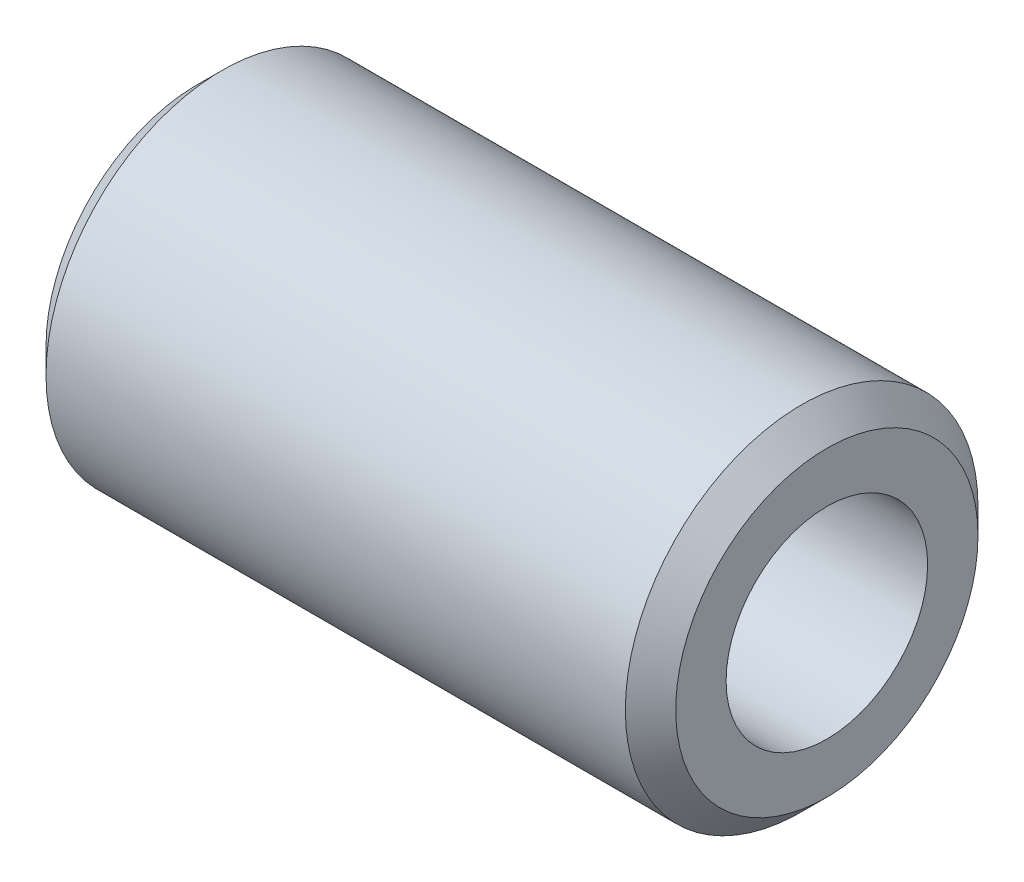
SolidWorks part; units mm, degrees
material "Nylon 101"
ref_plane "Спереди" through (0, 0, 0) normal (0, 0, 1) x (1, 0, 0)
ref_plane "Сверху" through (0, 0, 0) normal (0, 1, 0) x (1, 0, 0)
ref_plane "Справа" through (0, 0, 0) normal (1, 0, 0) x (0, 0, -1)
sketch "Эскиз1" plane through (0, 0, 0) normal (0, 0, 1) x (1, 0, 0)
  line L0 (0, 0) -> (-50000, 0) construction
  line L9 (0, 0) -> (0, 50000) construction
  line L10 (-12.5, 7) -> (12.5, 7)
  line L11 (12.5, 7) -> (12.5, 4)
  line L13 (-12.5, 4) -> (-12.5, 7)
  line L18 (-12.5, 4) -> (12.5, 4)
  dimension "D1" = 8
  dimension "D2" = 14
  dimension "D3" = 25
revolve "Повернуть1" add sketch "Эскиз1" angle 360 about L0
sketch "Эскиз2" plane through (12.5, 0, 0) normal (1, 0, 0) x (0, 0, -1)
  line L0 (-2.5, -3.1225) -> (2.5, -3.1225)
  line L1 (0, 1.648) -> (0, -0.5395) construction
  circle A0 centre (0, 0) radius 4 construction
  arc A1 (-2.5, -3.1225) -> (2.5, -3.1225) centre (0, 0) ccw
  dimension "D1" = 5
extrude "Бобышка-Вытянуть1" [suppressed] add sketch "Эскиз2" against normal through all
sketch "Эскиз7" plane through (-12.5, 0, 0) normal (-1, 0, 0) x (0, 0, 1)
  point P0 (0, 0)
hole_wizard "Диаметр отверстия Ø8.0 (8)1" positions "Эскиз7" profile "Эскиз6" hole size "Ø8.0" standard "IS"
sketch "Эскиз6" plane through (-12.5, 0, 0) normal (0, 1, 0) x (0, 0, 1)
  line L0 (0, 0) -> (0, 7.4034)
  line L1 (0, 7.4034) -> (4, 5)
  line L2 (4, 5) -> (4, 0.025)
  line L3 (4, 0.025) -> (4.025, 0)
  line L5 (4.025, 0) -> (0, 0)
  line L6 (-4, 0.025) -> (-4.025, 0) construction
  line L10 (0, 7.4034) -> (-4, 5) construction
  line L11 (0, -6.35) -> (0, 107.95) construction
  dimension "Диаметр отверстия" = 8
  dimension "Глубина отверстия" = 5
  dimension "Диаметр передней зенковки" = 8.05
  dimension "Угол передней зенковки" = 90
  dimension "Угол заточки сверла" = 118
ref_plane "Плоскость1" through (0, -7, 0) normal (0, -1, 0) x (-1, 0, 0)
sketch "Эскиз3" plane through (0, -7, 0) normal (0, -1, 0) x (-1, 0, 0)
  line L1 (7.5, -2.5) -> (-7.5, -2.5)
  line L2 (7.5, -2.5) -> (7.5, 2.5)
  line L3 (7.5, 2.5) -> (-7.5, 2.5)
  line L4 (-7.5, -2.5) -> (-7.5, 2.5)
  line L5 (7.5, -2.5) -> (-7.5, 2.5) construction
  line L6 (7.5, 2.5) -> (-7.5, -2.5) construction
  point P0 (1.1978, 0.3993)
  dimension "D1" = 5
  dimension "D2" = 15
extrude "Вырез-Вытянуть1" cut sketch "Эскиз3" against normal blind 4
fillet "Скругление1" radius 2.5 4 edges at (-7.5, -4.8304, 2.5) (-7.5, -4.8304, -2.5) (7.5, -4.8304, 2.5) (7.5, -4.8304, -2.5)
chamfer "Фаска1" distance 1 angle 45 2 edges at (12.5, 0, -7) (-12.5, 0, -7)
